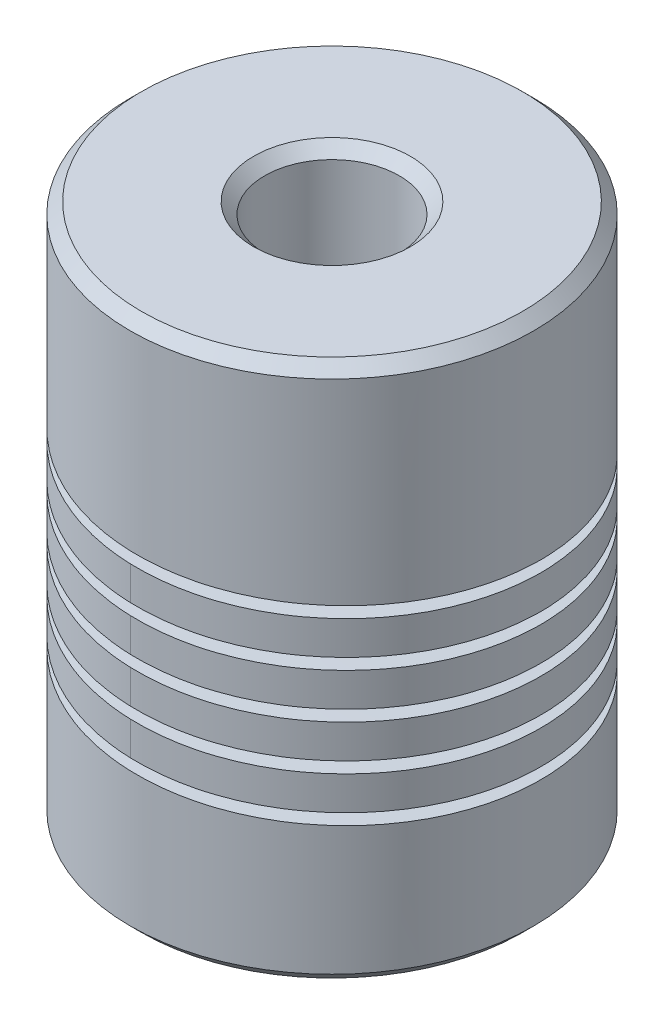
SolidWorks part; units mm, degrees
material "1060 Alloy"
ref_plane "Front Plane" through (0, 0, 0) normal (0, 0, 1) x (1, 0, 0)
ref_plane "Top Plane" through (0, 0, 0) normal (0, 1, 0) x (1, 0, 0)
ref_plane "Right Plane" through (0, 0, 0) normal (1, 0, 0) x (0, 0, -1)
sketch "Sketch1" plane through (0, 0, 0) normal (0, 1, 0) x (1, 0, 0)
  circle A0 centre (0, 0) radius 9
  dimension "D1" = 18
extrude "Boss-Extrude1" add sketch "Sketch1" along normal blind 24
sketch "Sketch2" plane through (0, 24, 0) normal (0, 1, 0) x (1, 0, 0)
  circle A0 centre (0, 0) radius 3
  dimension "D1" = 6
extrude "Cut-Extrude1" cut sketch "Sketch2" against normal through all
sketch "Sketch3" plane through (0, 0, 0) normal (0, -1, 0) x (1, 0, 0)
  circle A0 centre (0, 0) radius 4
  dimension "D1" = 8
extrude "Cut-Extrude2" cut sketch "Sketch3" against normal offset from surface (16 mm away) 8 up to face at (0, 24, 3)
chamfer "Chamfer1" distance 0.5 angle 45 4 edges at (0, 24, 3) (0, 24, 9) (0, 0, 9) (0, 0, -4)
sketch "Sketch10" plane through (0, 16, 0) normal (0, -1, 0) x (1, 0, 0)
  line L0 (0, -9) -> (0, -4) construction
  line L1 (0, -9) -> (0, -4) construction
  circle A0 centre (0, 0) radius 6.5
  circle A1 centre (0, 0) radius 4 construction
  circle A2 centre (0, 0) radius 9 construction
  point P10 (0, -6.5)
curve "Helix/Spiral1" pitch 2 height 10 turns 5
sketch "Sketch8" plane through (0, 0, 0) normal (1, 0, 0) x (0, 0, -1)
  line L0 (9, 0.5) -> (9, 23.5) construction
  line L1 (9, 16) -> (4, 16)
  line L2 (9, 16) -> (9, 15.5)
  line L3 (9, 15.5) -> (4, 15.5)
  line L4 (4, 16) -> (4, 15.5)
  line L5 (4, 0.5) -> (4, 16) construction
  line L6 (4, 0.5) -> (4, 16) construction
  line L8 (9, 0.5) -> (9, 23.5) construction
  line L9 (4, 15.5) -> (9, 16) construction
  line L10 (-4, 16) -> (4, 16) construction
  dimension "D2" = 0.5
sweep "Cut-Sweep2" cut profiles "Sketch8" path "Helix/Spiral1"
sketch "Sketch11" plane through (0, 0, 0) normal (1, 0, 0) x (0, 0, -1)
  circle A0 centre (0, 2.9729) radius 1.1902
  circle A1 centre (0, 20.3791) radius 1.9654
  dimension "D1" = 3.9309
